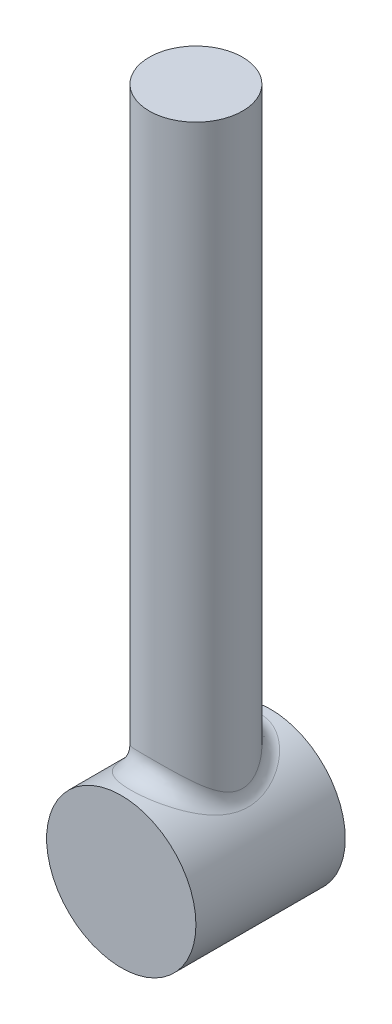
SolidWorks part; units mm, degrees
ref_plane "Front Plane" through (0, 0, 0) normal (0, 0, 1) x (1, 0, 0)
ref_plane "Top Plane" through (0, 0, 0) normal (0, 1, 0) x (1, 0, 0)
ref_plane "Right Plane" through (0, 0, 0) normal (1, 0, 0) x (0, 0, -1)
sketch "Sketch1" plane through (0, 0, 0) normal (0, 0, 1) x (1, 0, 0)
  circle A0 centre (0, 0) radius 4
  dimension "D1" = 8
extrude "Boss-Extrude1" add sketch "Sketch1" along normal blind 8
sketch "Sketch2" plane through (0, 0, 0) normal (0, 1, 0) x (1, 0, 0)
  circle A0 centre (0, -4) radius 2.5
  dimension "D1" = 5
extrude "Boss-Extrude2" add sketch "Sketch2" along normal blind 35
fillet "Fillet1" radius 1 1 edges at (0.6095, 3.9533, 6.4246)
